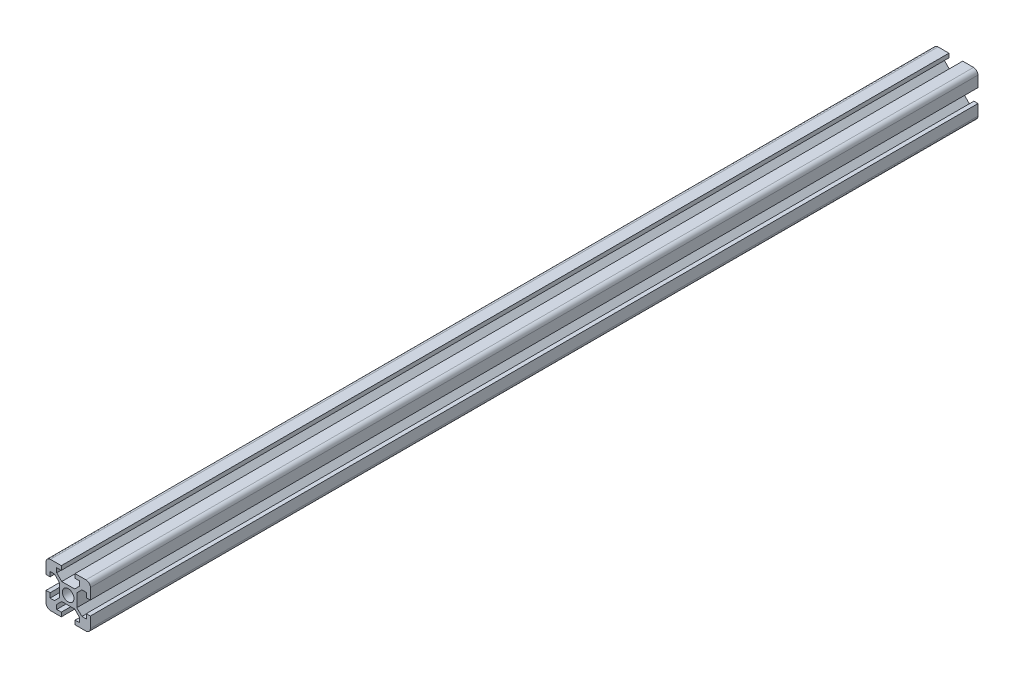
SolidWorks part; units mm, degrees
ref_plane "Front Plane" through (0, 0, 0) normal (0, 0, 1) x (1, 0, 0)
ref_plane "Top Plane" through (0, 0, 0) normal (0, 1, 0) x (1, 0, 0)
ref_plane "Right Plane" through (0, 0, 0) normal (1, 0, 0) x (0, 0, -1)
sketch "Sketch1" plane through (0, 0, 0) normal (0, 0, 1) x (1, 0, 0)
  line L1 (-3.9, 2.9101) -> (-6.1799, 5.19)
  line L2 (-8.15, 5.19) -> (-8.15, 3.1)
  line L3 (-8.15, 3.1) -> (-10, 3.1)
  line L4 (-10, 3.1) -> (-10, 10)
  line L5 (-10, 10) -> (-3.1, 10)
  line L6 (-3.1, 10) -> (-3.1, 8.15)
  line L7 (-3.1, 8.15) -> (-5.19, 8.15)
  line L8 (-5.19, 6.1799) -> (-2.9101, 3.9)
  line L10 (0, 15.4917) -> (0, -11.1126) construction
  line L11 (-16.3459, 0) -> (7.5931, 0) construction
  line L21 (16.3459, 0) -> (-7.5931, 0) construction
  line L39 (-8.15, 5.19) -> (-6.1799, 5.19)
  line L40 (-5.19, 6.1799) -> (-5.19, 8.15)
  line L41 (-3.9, 2.9101) -> (-3.9, -2.9101)
  line L42 (-2.9101, 3.9) -> (2.9101, 3.9)
  line L43 (-2.9101, -3.9) -> (2.9101, -3.9)
  line L44 (-5.19, -6.1799) -> (-5.19, -8.15)
  line L45 (-8.15, -5.19) -> (-6.1799, -5.19)
  line L46 (-5.19, -6.1799) -> (-2.9101, -3.9)
  line L47 (-3.1, -8.15) -> (-5.19, -8.15)
  line L48 (-3.1, -10) -> (-3.1, -8.15)
  line L49 (-10, -10) -> (-3.1, -10)
  line L50 (-10, -3.1) -> (-10, -10)
  line L51 (-8.15, -3.1) -> (-10, -3.1)
  line L52 (-8.15, -5.19) -> (-8.15, -3.1)
  line L53 (-3.9, -2.9101) -> (-6.1799, -5.19)
  line L54 (-16.3459, 0) -> (7.5931, 0) construction
  line L55 (3.9, -2.9101) -> (6.1799, -5.19)
  line L56 (8.15, -5.19) -> (8.15, -3.1)
  line L57 (8.15, -3.1) -> (10, -3.1)
  line L58 (10, -3.1) -> (10, -10)
  line L59 (10, -10) -> (3.1, -10)
  line L60 (3.1, -10) -> (3.1, -8.15)
  line L61 (3.1, -8.15) -> (5.19, -8.15)
  line L62 (5.19, -6.1799) -> (2.9101, -3.9)
  line L63 (8.15, -5.19) -> (6.1799, -5.19)
  line L64 (5.19, -6.1799) -> (5.19, -8.15)
  line L65 (3.9, 2.9101) -> (3.9, -2.9101)
  line L66 (5.19, 6.1799) -> (5.19, 8.15)
  line L67 (8.15, 5.19) -> (6.1799, 5.19)
  line L68 (5.19, 6.1799) -> (2.9101, 3.9)
  line L69 (3.1, 8.15) -> (5.19, 8.15)
  line L70 (3.1, 10) -> (3.1, 8.15)
  line L71 (10, 10) -> (3.1, 10)
  line L72 (10, 3.1) -> (10, 10)
  line L73 (8.15, 3.1) -> (10, 3.1)
  line L74 (8.15, 5.19) -> (8.15, 3.1)
  line L75 (3.9, 2.9101) -> (6.1799, 5.19)
  circle A0 centre (0, 0) radius 2.6
  point P0 (-3.9, 3.0606)
  point P19 (-3.9, 0)
  point P20 (-3.9, 0)
  point P37 (0, -3.9)
  point P38 (0, 3.9)
  point P46 (3.9, 0)
  point P50 (0, -3.9)
  point P53 (0, 3.9)
  dimension "D8" = 5.2
  dimension "D1" = 10
  dimension "D2" = 10
  dimension "D3" = 6.1
  dimension "D4" = 1.4
  dimension "D5" = 6.1
  dimension "D6" = 1.85
  dimension "D7" = 6.9
  dimension "D9" = 4.81
  dimension "D10" = 4.81
extrude "Boss-Extrude1" add sketch "Sketch1" against normal blind 400
fillet "Fillet1" radius 2 4 edges at (10, -10, -200) (-10, -10, -200) (10, 10, -200) (-10, 10, -200)
